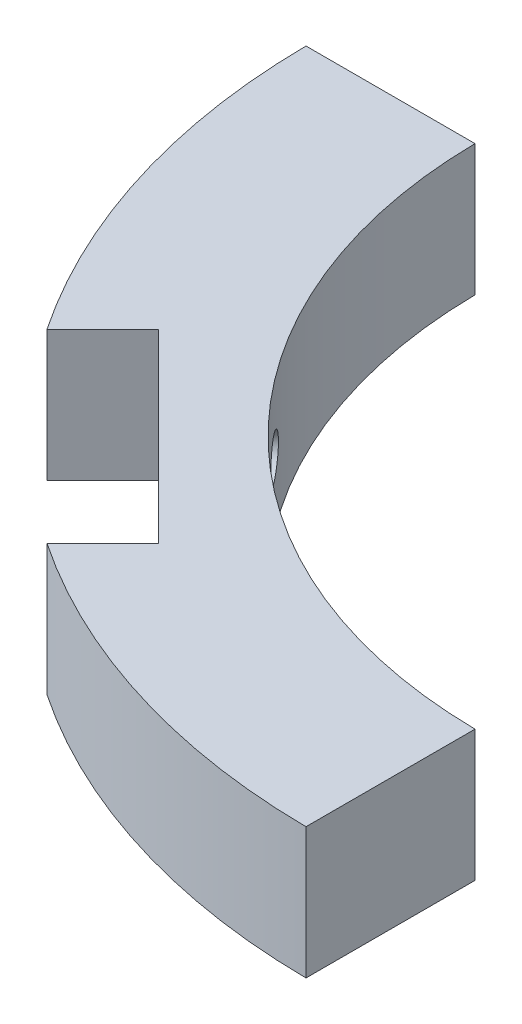
SolidWorks part; units mm, degrees
material "6061-T6 (SS)"
ref_plane "Front Plane" through (0, 0, 0) normal (0, 0, 1) x (1, 0, 0)
ref_plane "Top Plane" through (0, 0, 0) normal (0, 1, 0) x (1, 0, 0)
ref_plane "Right Plane" through (0, 0, 0) normal (1, 0, 0) x (0, 0, -1)
sketch "Sketch1" plane through (0, 0, 0) normal (0, 1, 0) x (1, 0, 0)
  line L0 (0, 0) -> (-24.5, 0) construction
  line L1 (0, 0) -> (0, -24.5) construction
  line L2 (-19.549, -0.2) -> (-25.9992, -0.2)
  line L3 (-0.2, -19.549) -> (-0.2, -25.9992)
  line L4 (-0.2, -0.2) -> (-24.5, -0.2) construction
  line L5 (-0.2, -0.2) -> (-0.2, -24.5) construction
  arc A0 (-19.549, -0.2) -> (-0.2, -19.549) centre (0, 0) ccw
  arc A1 (-25.9992, -0.2) -> (-0.2, -25.9992) centre (0, 0) ccw
  dimension "D1" = 39.1
  dimension "D2" = 52
  dimension "D3" = 0.2
extrude "Boss-Extrude1" add sketch "Sketch1" along normal mid plane 5
sketch "Sketch2" plane through (0, 2.5, 0) normal (0, 1, 0) x (1, 0, 0)
  line L0 (-18.3848, -18.3848) -> (0, 0) construction
  line L1 (-21.9203, -14.8492) -> (-14.8492, -21.9203)
  line L5 (-21.9203, -14.8492) -> (-19.4454, -12.3744)
  line L6 (-19.4454, -12.3744) -> (-12.3744, -19.4454)
  line L7 (-12.3744, -19.4454) -> (-14.8492, -21.9203)
  arc A0 (-25.9992, -0.2) -> (-0.2, -25.9992) centre (0, 0) ccw construction
  point P9 (-18.3848, -18.3848)
  dimension "D1" = 3.5
  dimension "D2" = 10
extrude "Cut-Extrude1" cut sketch "Sketch2" against normal through all
sketch "Sketch3" plane through (-15.9099, 0, 15.9099) normal (-0.7071, 0, 0.7071) x (0.7071, 0, 0.7071)
  line L0 (-5, 0) -> (5, 0) construction
  line L1 (-5, -2.5) -> (-5, 2.5) construction
  line L2 (5, 2.5) -> (5, -2.5) construction
  line L3 (0, 0) -> (0, 2.5) construction
  line L4 (5, 2.5) -> (-5, 2.5) construction
  point P6 (-2.5, 0)
  point P12 (2.5, 0)
  dimension "D1" = 2.5
hole_wizard "Tap Drill for M2x0.4 Tap1" positions "3DSketch1" profile "Sketch4" hole size "M2x0.4" standard "ANSI Metric" end condition through all
sketch3d "3DSketch1"
  point P0 (-17.6777, 0, 14.1421)
  point P3 (-14.1421, 0, 17.6777)
sketch "Sketch4" plane through (-17.6777, 0, 14.1421) normal (0, 1, 0) x (0.7071, 0, 0.7071)
  line L0 (0, 0) -> (0, 22.2172)
  line L1 (0, 22.2172) -> (0.8, 22.2172)
  line L2 (0.8, 22.2172) -> (0.8, 0)
  line L5 (0.8, 0) -> (0, 0)
  line L11 (0, -6.35) -> (0, 107.95) construction
  dimension "Thru Hole Dia." = 1.6
  dimension "Thru Hole Depth" = 22.2172
thread "Thread1" pitch 0.4 method extrude profile "Thread Profile1" start angle 0, offset 0, length 0.8, pitch 0.4, diameter 1.6
ref_plane "Plane1" through (-18.2434, 0, 13.5765) normal (0, -1, 0) x (-0.7071, 0, -0.7071)
sketch "Thread Profile1" plane through (-18.2434, 0, 13.5765) normal (0, -1, 0) x (-0.7071, 0, -0.7071)
  line L0 (0, 0) -> (0, 0.4) construction
  line L11 (0, 0) -> (0, 0.35)
  line L12 (0, 0.35) -> (-0.2165, 0.225)
  line L13 (-0.2165, 0.225) -> (-0.2165, 0.125)
  line L15 (-0.2165, 0.125) -> (0, 0)
  line L17 (-0.2165, 0.175) -> (0, 0.175) construction
  point P2 (0, 0)
  dimension "Pitch" = 0.4
  dimension "Profile_Angle" = 60
  dimension "Profile_Land" = 0.1
  dimension "Profile_Height" = 0.2165
thread "Thread2" pitch 0.4 method extrude profile "Thread Profile2" start angle 0, offset 0, length 0.8, pitch 0.4, diameter 1.6
ref_plane "Plane2" through (-14.7078, 0, 17.112) normal (0, -1, 0) x (-0.7071, 0, -0.7071)
sketch "Thread Profile2" plane through (-14.7078, 0, 17.112) normal (0, -1, 0) x (-0.7071, 0, -0.7071)
  line L0 (0, 0) -> (0, 0.4) construction
  line L11 (0, 0) -> (0, 0.35)
  line L12 (0, 0.35) -> (-0.2165, 0.225)
  line L13 (-0.2165, 0.225) -> (-0.2165, 0.125)
  line L15 (-0.2165, 0.125) -> (0, 0)
  line L17 (-0.2165, 0.175) -> (0, 0.175) construction
  point P2 (0, 0)
  dimension "Pitch" = 0.4
  dimension "Profile_Angle" = 60
  dimension "Profile_Land" = 0.1
  dimension "Profile_Height" = 0.2165
